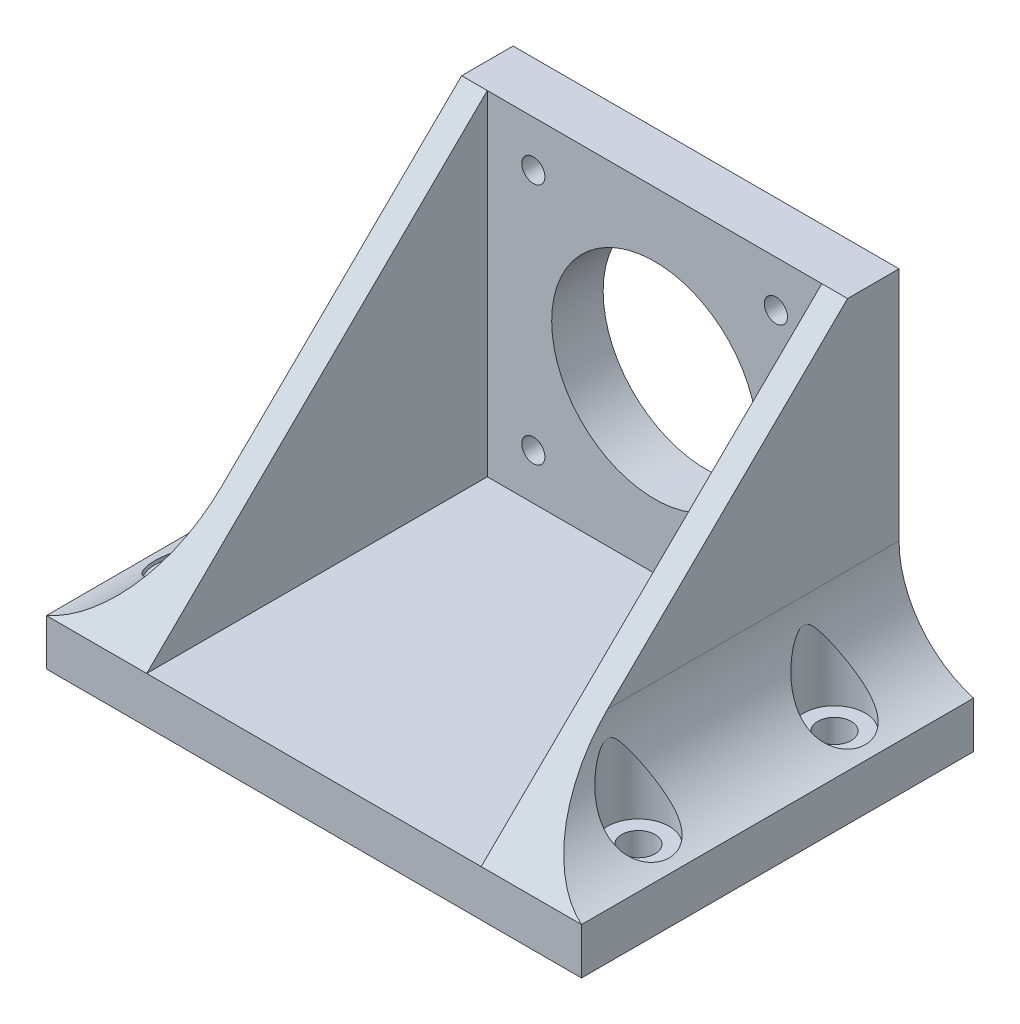
SolidWorks part; units mm, degrees
ref_plane "Front Plane" through (0, 0, 0) normal (0, 0, 1) x (1, 0, 0)
ref_plane "Top Plane" through (0, 0, 0) normal (0, 1, 0) x (1, 0, 0)
ref_plane "Right Plane" through (0, 0, 0) normal (1, 0, 0) x (0, 0, -1)
sketch "Sketch1" plane through (0, 0, 0) normal (0, 0, 1) x (1, 0, 0)
  line L1 (-32.5, 32.5) -> (32.5, 32.5)
  line L2 (-32.5, 32.5) -> (-32.5, -32.5)
  line L3 (-32.5, -32.5) -> (32.5, -32.5)
  line L4 (32.5, 32.5) -> (32.5, -32.5)
  line L5 (-32.5, 32.5) -> (32.5, -32.5) construction
  line L6 (-32.5, -32.5) -> (32.5, 32.5) construction
  circle A0 centre (0, 0) radius 20
  circle A1 centre (23.57, 23.57) radius 2.25
  circle A2 centre (-23.57, 23.57) radius 2.25
  circle A3 centre (-23.57, -23.57) radius 2.25
  circle A4 centre (23.57, -23.57) radius 2.25
  point P0 (0, 0)
  dimension "D1" = 2
  dimension "D2" = 2
extrude "Boss-Extrude1" add sketch "Sketch1" along normal blind 10
sketch "Sketch2" plane through (0, 0, 10) normal (0, 0, 1) x (1, 0, 0)
  line L0 (0, -32.5) -> (-52, -32.5)
  line L1 (-32.5, -32.5) -> (32.5, -32.5) construction
  line L2 (-52, -32.5) -> (-52, -42.5)
  line L3 (-52, -42.5) -> (52, -42.5)
  line L4 (52, -42.5) -> (52, -32.5)
  line L5 (52, -32.5) -> (0, -32.5)
extrude "Boss-Extrude2" add sketch "Sketch2" along normal blind 66.2 and the other way blind 10
sketch "Sketch4" plane through (32.5, 0, 0) normal (1, 0, 0) x (0, 0, -1)
  line L0 (0, -32.5) -> (-76.2, -32.5) construction
  line L1 (0, -32.5) -> (-76.2, -32.5)
  line L2 (0, -32.5) -> (0, 32.5) construction
  line L3 (-10, 32.5) -> (0, 32.5) construction
  line L4 (0, -32.5) -> (0, 32.5)
  line L5 (-10, 32.5) -> (0, 32.5)
  line L6 (-10, 32.5) -> (-76.2, -32.5)
extrude "Boss-Extrude3" add sketch "Sketch4" along normal blind 5
sketch "Sketch5" plane through (-32.5, 0, 0) normal (-1, 0, 0) x (0, 0, 1)
  line L0 (10, 32.5) -> (0, 32.5) construction
  line L1 (0, 32.5) -> (0, -32.5) construction
  line L2 (0, -32.5) -> (76.2, -32.5) construction
  line L3 (10, 32.5) -> (0, 32.5)
  line L4 (0, 32.5) -> (0, -32.5)
  line L5 (0, -32.5) -> (76.2, -32.5)
  line L6 (10, 32.5) -> (76.2, -32.5)
extrude "Boss-Extrude4" add sketch "Sketch5" along normal blind 5
fillet "Fillet1" radius 20 2 edges at (37.5, -32.5, 38.1) (-37.5, -32.5, 38.1)
sketch "Sketch3" plane through (0, -42.5, 0) normal (0, -1, 0) x (1, 0, 0)
  circle A0 centre (44, 19.05) radius 3.25
  circle A1 centre (-44, 19.05) radius 3.25
  circle A2 centre (-44, 57.15) radius 3.25
  circle A3 centre (44, 57.15) radius 3.25
  dimension "D1" = 2
  dimension "D2" = 2
extrude "Cut-Extrude1" cut sketch "Sketch3" against normal through all
ref_plane "Plane1" through (0, -11.5, 0) normal (0, 1, 0) x (1, 0, 0)
sketch "Sketch6" plane through (0, -11.5, 0) normal (0, 1, 0) x (1, 0, 0)
  circle A0 centre (44, -19.05) radius 3.25 construction
  circle A1 centre (44, -57.15) radius 3.25 construction
  circle A2 centre (-44, -57.15) radius 3.25 construction
  circle A3 centre (-44, -19.05) radius 3.25 construction
  circle A4 centre (44, -19.05) radius 3.25
  circle A5 centre (44, -57.15) radius 3.25
  circle A6 centre (-44, -57.15) radius 3.25
  circle A7 centre (-44, -19.05) radius 3.25
  circle A8 centre (-44, -19.05) radius 6
  circle A9 centre (-44, -57.15) radius 6
  circle A10 centre (44, -57.15) radius 6
  circle A11 centre (44, -19.05) radius 6
extrude "Cut-Extrude2" cut sketch "Sketch6" against normal up to surface (21 mm away) up to face at (0, -32.5, 43.1)
chamfer "Chamfer1" distance 1 angle 45 8 edges at (0, -42.5, 0) (-52, -42.5, 38.1) (0, -42.5, 76.2) (52, -42.5, 38.1) (44, -42.5, 15.8) (-44, -42.5, 15.8) (-44, -42.5, 53.9) (44, -42.5, 53.9)
